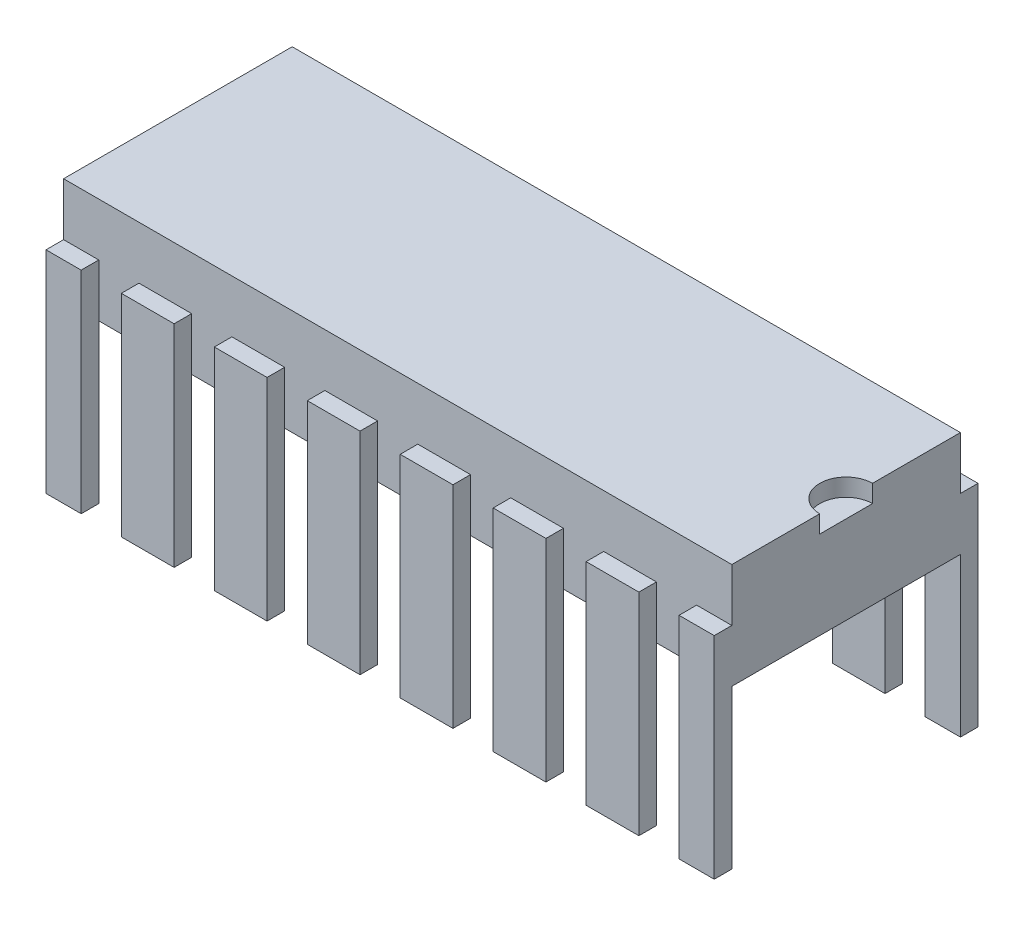
SolidWorks part; units mm, degrees
ref_plane "Front" through (0, 0, 0) normal (0, 0, 1) x (1, 0, 0)
ref_plane "Top" through (0, 0, 0) normal (0, 1, 0) x (1, 0, 0)
ref_plane "Right" through (0, 0, 0) normal (1, 0, 0) x (0, 0, -1)
sketch "Эскиз1" plane through (0, 0, 0) normal (0, 1, 0) x (1, 0, 0)
  line L0 (-9.5, 0) -> (9.5, 0) construction
  line L1 (-9.5, 3.25) -> (9.5, 3.25)
  line L2 (-9.5, 3.25) -> (-9.5, -3.25)
  line L3 (-9.5, -3.25) -> (9.5, -3.25)
  line L4 (9.5, 3.25) -> (9.5, -3.25)
  line L5 (-9.5, 3.25) -> (9.5, -3.25) construction
  line L6 (-9.5, -3.25) -> (9.5, 3.25) construction
  line L7 (0, 3.25) -> (0, -3.25) construction
  line L8 (-8.5, 3.75) -> (-7.3571, 3.75) construction
  line L9 (-9.5, 3.25) -> (-8.5, 3.25)
  line L10 (-9.5, 3.25) -> (-9.5, 3.75)
  line L11 (-9.5, 3.75) -> (-8.5, 3.75)
  line L12 (-8.5, 3.25) -> (-8.5, 3.75)
  line L13 (-7.3571, 3.25) -> (-5.8571, 3.25)
  line L14 (-7.3571, 3.25) -> (-7.3571, 3.75)
  line L15 (-7.3571, 3.75) -> (-5.8571, 3.75)
  line L16 (-5.8571, 3.25) -> (-5.8571, 3.75)
  line L17 (-4.7143, 3.25) -> (-3.2143, 3.25)
  line L18 (-4.7143, 3.25) -> (-4.7143, 3.75)
  line L19 (-4.7143, 3.75) -> (-3.2143, 3.75)
  line L20 (-3.2143, 3.25) -> (-3.2143, 3.75)
  line L21 (-2.0714, 3.25) -> (-0.5714, 3.25)
  line L22 (-2.0714, 3.25) -> (-2.0714, 3.75)
  line L23 (-2.0714, 3.75) -> (-0.5714, 3.75)
  line L24 (-0.5714, 3.25) -> (-0.5714, 3.75)
  line L25 (0.5714, 3.25) -> (2.0714, 3.25)
  line L26 (0.5714, 3.25) -> (0.5714, 3.75)
  line L27 (0.5714, 3.75) -> (2.0714, 3.75)
  line L28 (2.0714, 3.25) -> (2.0714, 3.75)
  line L29 (3.2143, 3.25) -> (4.7143, 3.25)
  line L30 (3.2143, 3.25) -> (3.2143, 3.75)
  line L31 (3.2143, 3.75) -> (4.7143, 3.75)
  line L32 (4.7143, 3.25) -> (4.7143, 3.75)
  line L33 (5.8571, 3.25) -> (7.3571, 3.25)
  line L34 (5.8571, 3.25) -> (5.8571, 3.75)
  line L35 (5.8571, 3.75) -> (7.3571, 3.75)
  line L36 (7.3571, 3.25) -> (7.3571, 3.75)
  line L37 (9.5, 3.25) -> (8.5, 3.25)
  line L38 (9.5, 3.25) -> (9.5, 3.75)
  line L39 (9.5, 3.75) -> (8.5, 3.75)
  line L40 (8.5, 3.25) -> (8.5, 3.75)
  line L41 (-9.5, -3.25) -> (-8.5, -3.25)
  line L42 (-9.5, -3.25) -> (-9.5, -3.75)
  line L43 (-9.5, -3.75) -> (-8.5, -3.75)
  line L44 (-8.5, -3.25) -> (-8.5, -3.75)
  line L45 (-7.3571, -3.25) -> (-5.8571, -3.25)
  line L46 (-7.3571, -3.25) -> (-7.3571, -3.75)
  line L47 (-7.3571, -3.75) -> (-5.8571, -3.75)
  line L48 (-5.8571, -3.25) -> (-5.8571, -3.75)
  line L49 (-4.7143, -3.25) -> (-3.2143, -3.25)
  line L50 (-4.7143, -3.25) -> (-4.7143, -3.75)
  line L51 (-4.7143, -3.75) -> (-3.2143, -3.75)
  line L52 (-3.2143, -3.25) -> (-3.2143, -3.75)
  line L53 (-2.0714, -3.25) -> (-0.5714, -3.25)
  line L54 (-2.0714, -3.25) -> (-2.0714, -3.75)
  line L55 (-2.0714, -3.75) -> (-0.5714, -3.75)
  line L56 (-0.5714, -3.25) -> (-0.5714, -3.75)
  line L57 (0.5714, -3.25) -> (2.0714, -3.25)
  line L58 (0.5714, -3.25) -> (0.5714, -3.75)
  line L59 (0.5714, -3.75) -> (2.0714, -3.75)
  line L60 (2.0714, -3.25) -> (2.0714, -3.75)
  line L61 (3.2143, -3.25) -> (4.7143, -3.25)
  line L62 (3.2143, -3.25) -> (3.2143, -3.75)
  line L63 (3.2143, -3.75) -> (4.7143, -3.75)
  line L64 (4.7143, -3.25) -> (4.7143, -3.75)
  line L65 (5.8571, -3.25) -> (7.3571, -3.25)
  line L66 (5.8571, -3.25) -> (5.8571, -3.75)
  line L67 (5.8571, -3.75) -> (7.3571, -3.75)
  line L68 (7.3571, -3.25) -> (7.3571, -3.75)
  line L69 (9.5, -3.25) -> (8.5, -3.25)
  line L70 (9.5, -3.25) -> (9.5, -3.75)
  line L71 (9.5, -3.75) -> (8.5, -3.75)
  line L72 (8.5, -3.25) -> (8.5, -3.75)
  line L73 (-5.8571, 3.75) -> (-4.7143, 3.75) construction
  line L74 (-3.2143, 3.75) -> (-2.0714, 3.75) construction
  line L75 (-0.5714, 3.75) -> (0.5714, 3.75) construction
  line L76 (2.0714, 3.75) -> (3.2143, 3.75) construction
  line L77 (4.7143, 3.75) -> (5.8571, 3.75) construction
  line L78 (7.3571, 3.75) -> (8.5, 3.75) construction
  line L79 (8.5, -3.75) -> (7.3571, -3.75) construction
  line L80 (5.8571, -3.75) -> (4.7143, -3.75) construction
  line L81 (3.2143, -3.75) -> (2.0714, -3.75) construction
  line L82 (-0.5714, -3.75) -> (0.5714, -3.75) construction
  line L83 (-2.0714, -3.75) -> (-3.2143, -3.75) construction
  line L84 (-4.7143, -3.75) -> (-5.8571, -3.75) construction
  line L85 (-7.3571, -3.75) -> (-8.5, -3.75) construction
  circle A0 centre (9.5, 0) radius 0.75
  point P0 (0, 0)
  dimension "D3" = 1.5
  dimension "D1" = 19
  dimension "D2" = 6.5
  dimension "D4" = 0.5
  dimension "D5" = 1
  dimension "D6" = 1.5
extrude "Бобышка-Вытянуть1" add sketch "Эскиз1" along normal blind 3 contours A0 L4 L1 L2 L3 region at (-0.0662, 0, 0)
extrude "Бобышка-Вытянуть2" add sketch "Эскиз1<3>" along normal blind 2.5 contours L4 A0 region at (9.1817, 0, 0)
sketch "Эскиз1<3>" plane through (0, 0, 0) normal (0, 1, 0) x (1, 0, 0) same geometry as "Эскиз1"
extrude "Бобышка-Вытянуть3" add sketch "Эскиз1<4>" against normal blind 6 from offset 1.5 contours L1 L12 L11 L10 | L1 L16 L15 L14 | L1 L20 L19 L18 | L1 L28 L27 L26 | L1 L32 L31 L30 | L1 L36 L35 L34 | L40 L1 L38 L39 | L3 L72 L71 L70 | L68 L3 L66 L67 | L64 L3 L62 L63 | L60 L3 L58 L59 | L52 L3 L50 L51 | L48 L3 L46 L47 | L44 L3 L42 L43 | L23 L24 L21 L22 | L56 L55 L54 L53 region at (-9, 0, -3.5) region at (-9, 0, 3.5) region at (-6.6071, 0, -3.5) region at (-6.6071, 0, 3.5) region at (-3.9643, 0, -3.5) region at (-3.9643, 0, 3.5) region at (1.3214, 0, -3.5) region at (1.3214, 0, 3.5) region at (3.9643, 0, -3.5) region at (3.9643, 0, 3.5) region at (6.6071, 0, -3.5) region at (6.6071, 0, 3.5) region at (9, 0, -3.5) region at (9, 0, 3.5)
sketch "Эскиз1<4>" plane through (0, 0, 0) normal (0, 1, 0) x (1, 0, 0) same geometry as "Эскиз1"
